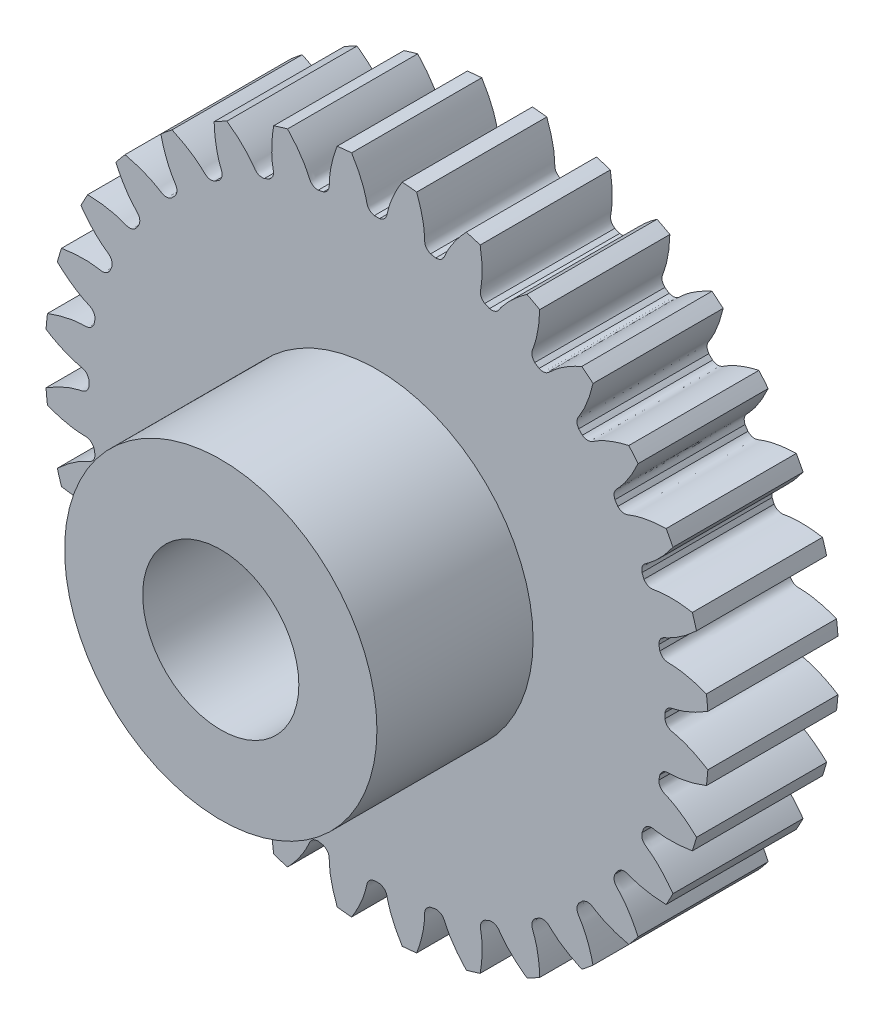
SolidWorks part; units mm, degrees
ref_plane "前视基准面" through (0, 0, 0) normal (0, 0, 1) x (1, 0, 0)
ref_plane "上视基准面" through (0, 0, 0) normal (0, 1, 0) x (1, 0, 0)
ref_plane "右视基准面" through (0, 0, 0) normal (1, 0, 0) x (0, 0, -1)
other "Configuration Table"
sketch "草图1" plane through (0, 0, 0) normal (0, 0, 1) x (1, 0, 0)
  circle A0 centre (0, 0) radius 12.75
extrude "凸台-拉伸1" add sketch "草图1" along normal blind 5
ref_axis "基准轴1" through (0, 0, -0.25) along (0, 0, 1)
sketch "草图2" plane through (0, 0, 0) normal (0, 0, 1) x (1, 0, 0)
  line L0 (0, 0) -> (0, 12.75) construction
  circle A0 centre (0, 0) radius 12.75 construction
  arc A1 (0.1005, 11.062) -> (-0.1005, 11.062) centre (0, 0) ccw
  arc A2 (2.5148, 14.4522) -> (-2.5148, 14.4522) centre (0, 0) ccw
  spline S0 degree 3 poles (0.1005, 11.062) (0.3666, 11.1264) (0.3813, 11.3193) (0.4301, 11.5206) (0.4428, 11.569) (0.4577, 11.6215) (0.475, 11.6781) (0.4948, 11.7385) (0.5173, 11.8028) (0.5426, 11.8709) (0.571, 11.9426) (0.6025, 12.018) (0.6374, 12.0968) (0.6758, 12.1789) (0.7177, 12.2644) (0.7634, 12.353) (0.8131, 12.4446) (0.8668, 12.5392) (0.9247, 12.6365) (0.9868, 12.7365) (1.0535, 12.839) (1.1247, 12.9439) (1.2006, 13.051) (1.2813, 13.1602) (1.3669, 13.2713) (1.4576, 13.3842) (1.5534, 13.4988) (1.6544, 13.6148) (1.7607, 13.7321) (1.8725, 13.8506) (1.9898, 13.97) (2.1126, 14.0902) (2.2862, 14.2533) (2.4217, 14.3731) (2.5148, 14.4522) knots 0 0 0 0 0.124533 0.135329 0.147193 0.160126 0.174128 0.189198 0.205337 0.222544 0.24082 0.260164 0.280577 0.302059 0.324609 0.348227 0.372914 0.39867 0.425494 0.453386 0.482348 0.512377 0.543476 0.575642 0.608878 0.643181 0.678554 0.714995 0.752504 0.791082 0.830729 0.871444 0.913227 1 1 1 1
  spline S1 degree 3 poles (-0.1005, 11.062) (-0.3666, 11.1264) (-0.3813, 11.3193) (-0.4301, 11.5206) (-0.4428, 11.569) (-0.4577, 11.6215) (-0.475, 11.6781) (-0.4948, 11.7385) (-0.5173, 11.8028) (-0.5426, 11.8709) (-0.571, 11.9426) (-0.6025, 12.018) (-0.6374, 12.0968) (-0.6758, 12.1789) (-0.7177, 12.2644) (-0.7634, 12.353) (-0.8131, 12.4446) (-0.8668, 12.5392) (-0.9247, 12.6365) (-0.9868, 12.7365) (-1.0535, 12.839) (-1.1247, 12.9439) (-1.2006, 13.051) (-1.2813, 13.1602) (-1.3669, 13.2713) (-1.4576, 13.3842) (-1.5534, 13.4988) (-1.6544, 13.6148) (-1.7607, 13.7321) (-1.8725, 13.8506) (-1.9898, 13.97) (-2.1126, 14.0902) (-2.2862, 14.2533) (-2.4217, 14.3731) (-2.5148, 14.4522) knots 0 0 0 0 0.124533 0.135329 0.147193 0.160126 0.174128 0.189198 0.205337 0.222544 0.24082 0.260164 0.280577 0.302059 0.324609 0.348227 0.372914 0.39867 0.425494 0.453386 0.482348 0.512377 0.543476 0.575642 0.608878 0.643181 0.678554 0.714995 0.752504 0.791082 0.830729 0.871444 0.913227 1 1 1 1
extrude "切除-拉伸1" cut sketch "草图2" along normal through all
pattern_circular "阵列(圆周)1" count 32 every 11.25 about axis through (0, 0, -0.25) along (0, 0, 1) of "切除-拉伸1"
sketch "草图3" plane through (0, 0, 0) normal (0, 0, 1) x (1, 0, 0)
  circle A0 centre (0, 0) radius 12 construction
  dimension "Dn" = 24
sketch "草图4" plane through (0, 0, 5) normal (0, 0, 1) x (1, 0, 0)
  circle A0 centre (0, 0) radius 6
  dimension "D1" = 12
extrude "凸台-拉伸2" add sketch "草图4" along normal blind 6
sketch "草图5" plane through (0, 0, 11) normal (0, 0, 1) x (1, 0, 0)
  circle A0 centre (0, 0) radius 3
  dimension "D1" = 6
extrude "切除-拉伸2" cut sketch "草图5" against normal through all
